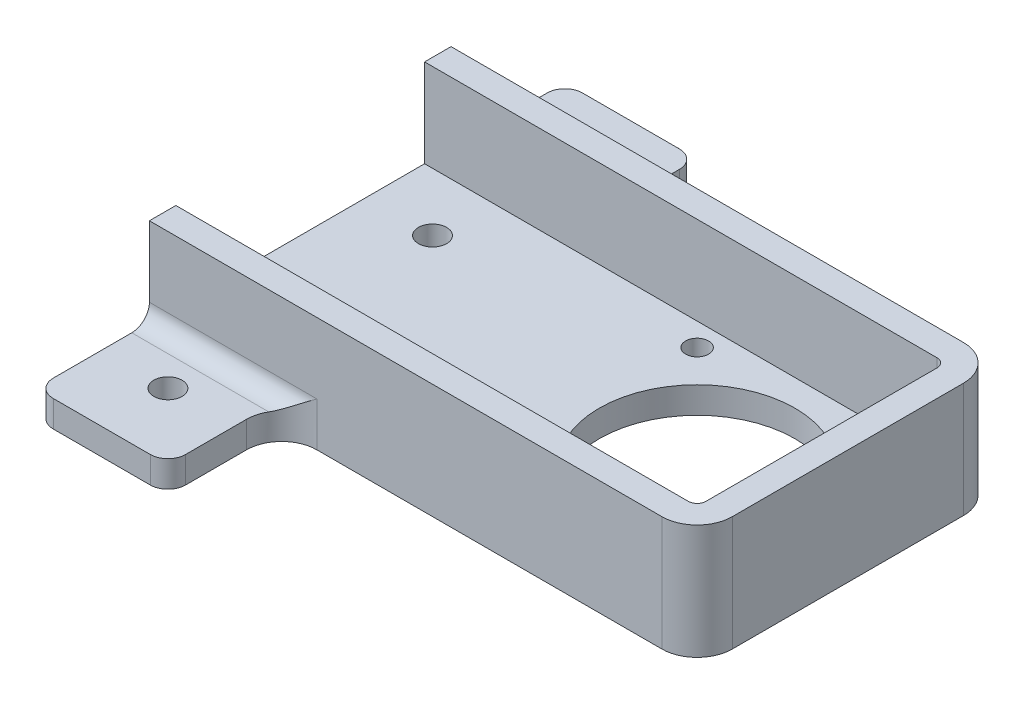
SolidWorks part; units mm, degrees
ref_plane "Front Plane" through (0, 0, 0) normal (0, 0, 1) x (1, 0, 0)
ref_plane "Top Plane" through (0, 0, 0) normal (0, 1, 0) x (1, 0, 0)
ref_plane "Right Plane" through (0, 0, 0) normal (1, 0, 0) x (0, 0, -1)
sketch "Sketch1" plane through (0, 0, 0) normal (0, 1, 0) x (1, 0, 0)
  line L0 (0, 0) -> (15, 0)
  line L2 (62.1, 12.9) -> (62.1, 47.1)
  line L4 (15, 60) -> (0, 60)
  line L5 (0, 60) -> (0, 0)
  line L6 (62.1, 47.1) -> (15, 47.1)
  line L7 (15, 47.1) -> (15, 60)
  line L8 (62.1, 12.9) -> (15, 12.9)
  line L9 (15, 12.9) -> (15, 0)
  point P2 (27.9, 47.1)
  point P9 (62.1, 30)
  point P10 (0, 30)
  point P11 (16.3085, 47.1)
  point P13 (16.8149, 12.9)
  dimension "D1" = 62.1
  dimension "D2" = 15
  dimension "D3" = 60
  dimension "D4" = 34.2
extrude "Boss-Extrude1" add sketch "Sketch1" along normal blind 3
sketch "Sketch2" plane through (0, 3, 0) normal (0, 1, 0) x (1, 0, 0)
  line L0 (0, 60) -> (0, 0) construction
  line L1 (15, 60) -> (0, 60) construction
  line L2 (0, 0) -> (15, 0) construction
  circle A0 centre (7.5, 52.5) radius 1.6
  circle A1 centre (7.5, 37.5) radius 1.6
  circle A2 centre (7.5, 7.5) radius 1.6
  circle A3 centre (7.5, 22.5) radius 1.6
  point P6 (0, 0)
  dimension "D1" = 3.2
  dimension "D2" = 7.5
  dimension "D3" = 7.5
  dimension "D4" = 7.5
  dimension "D5" = 15
  dimension "D6" = 15
extrude "Cut-Extrude1" cut sketch "Sketch2" against normal through all
sketch "Sketch3" plane through (0, 3, 0) normal (0, 1, 0) x (1, 0, 0)
  line L0 (62.1, 12.9) -> (15, 12.9)
  line L1 (15, 12.9) -> (0, 12.9)
  line L2 (0, 60) -> (0, 0) construction
  line L3 (0, 12.9) -> (0, 15.9)
  line L4 (0, 15.9) -> (59.1, 15.9)
  line L5 (59.1, 15.9) -> (59.1, 44.1)
  line L6 (59.1, 44.1) -> (0, 44.1)
  line L7 (0, 44.1) -> (0, 47.1)
  line L8 (0, 47.1) -> (62.1, 47.1)
  line L9 (62.1, 47.1) -> (15, 47.1) construction
  line L10 (62.1, 12.9) -> (62.1, 47.1) construction
  line L11 (62.1, 47.1) -> (62.1, 12.9)
  dimension "D1" = 3
  dimension "D2" = 3
  dimension "D3" = 3
extrude "Boss-Extrude2" add sketch "Sketch3" along normal blind 10
sketch "Sketch5" plane through (0, 3, 0) normal (0, 1, 0) x (1, 0, 0)
  line L0 (59.1, 44.1) -> (59.1, 15.9) construction
  circle A0 centre (45, 30) radius 11.1
  point P5 (59.1, 30)
  dimension "D1" = 22.2
  dimension "D2" = 14.1
extrude "Cut-Extrude2" cut sketch "Sketch5" against normal up to next
sketch "Sketch6" plane through (0, 3, 0) normal (0, 1, 0) x (1, 0, 0)
  line L0 (45, 44.1) -> (45, 15.9) construction
  line L1 (0, 44.1) -> (59.1, 44.1) construction
  line L2 (59.1, 15.9) -> (0, 15.9) construction
  line L3 (59.1, 44.1) -> (59.1, 15.9) construction
  line L4 (59.1, 30) -> (27.5371, 30) construction
  circle A0 centre (56.5, 41.5) radius 1.3
  circle A1 centre (33.5, 41.5) radius 1.3
  circle A2 centre (33.5, 18.5) radius 1.3
  circle A3 centre (56.5, 18.5) radius 1.3
  dimension "D2" = 2.6
  dimension "D1" = 14.1
  dimension "D3" = 23
  dimension "D4" = 23
extrude "Cut-Extrude3" cut sketch "Sketch6" against normal up to next
fillet "Fillet1" radius 1 2 edges at (59.1, 8, -15.9) (59.1, 8, -44.1)
fillet "Fillet2" radius 4 2 edges at (62.1, 6.5, -12.9) (62.1, 6.5, -47.1)
fillet "Fillet3" radius 4 2 edges at (15, 1.5, -47.1) (15, 1.5, -12.9)
fillet "Fillet4" radius 2 2 edges at (9.5, 3, -12.9) (9.5, 3, -47.1)
fillet "Fillet5" radius 2 4 edges at (0, 1.5, -60) (15, 1.5, -60) (0, 1.5, 0) (15, 1.5, 0)
